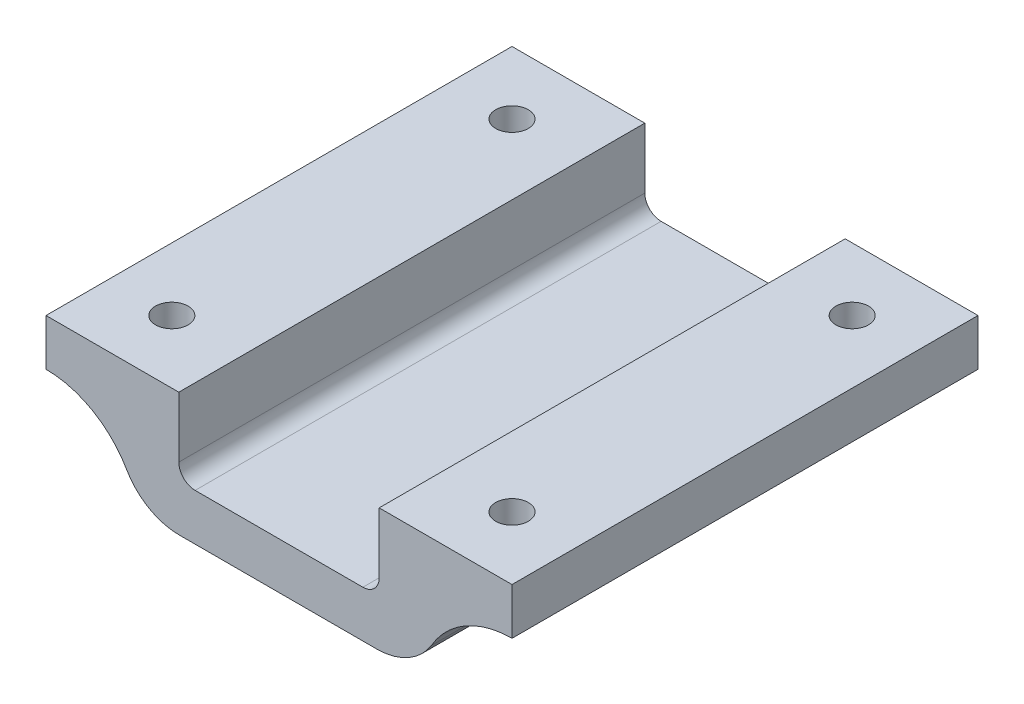
SolidWorks part; units mm, degrees
ref_plane "Front Plane" through (0, 0, 0) normal (0, 0, 1) x (1, 0, 0)
ref_plane "Top Plane" through (0, 0, 0) normal (0, 1, 0) x (1, 0, 0)
ref_plane "Right Plane" through (0, 0, 0) normal (1, 0, 0) x (0, 0, -1)
sketch "Sketch1" plane through (0, 0, 0) normal (0, 0, 1) x (1, 0, 0)
  line L0 (15, 13.2239) -> (35, 13.2239) construction
  line L1 (50, 10.2246) -> (50, 5.2246)
  line L2 (35.75, 10.2246) -> (50, 10.2246)
  line L3 (35.75, 3.7246) -> (35.75, 10.2246)
  line L4 (15, 22.2239) -> (15, 4.2239)
  line L5 (16, 3.2239) -> (34, 3.2239)
  line L6 (35, 4.2239) -> (35, 22.2239)
  line L7 (34, 23.2239) -> (16, 23.2239)
  line L8 (15, 22.2239) -> (15, 4.2239) construction
  line L9 (16, 3.2239) -> (34, 3.2239) construction
  line L10 (35, 4.2239) -> (35, 22.2239) construction
  line L11 (34, 23.2239) -> (16, 23.2239) construction
  line L12 (16, 1.9746) -> (34, 1.9746)
  line L13 (14.25, 10.2246) -> (14.25, 3.7246)
  line L14 (0, 10.2246) -> (14.25, 10.2246)
  line L15 (0, 5.2246) -> (0, 10.2246)
  line L16 (37.0096, 28.7233) -> (12.9904, 28.7233)
  line L17 (0, 21.2233) -> (0, 16.2233)
  line L18 (0, 16.2233) -> (14.25, 16.2233)
  line L19 (14.25, 16.2233) -> (14.25, 22.7233)
  line L20 (16, 24.4733) -> (34, 24.4733)
  line L21 (35.75, 22.7233) -> (35.75, 16.2233)
  line L22 (35.75, 16.2233) -> (50, 16.2233)
  line L23 (50, 16.2233) -> (50, 21.2233)
  line L24 (37.0096, 28.7233) -> (12.9904, 28.7233) construction
  line L25 (0, 21.2233) -> (0, 16.2233) construction
  line L26 (0, 16.2233) -> (14.25, 16.2233) construction
  line L27 (14.25, 16.2233) -> (14.25, 22.7233) construction
  line L28 (16, 24.4733) -> (34, 24.4733) construction
  line L29 (35.75, 22.7233) -> (35.75, 16.2233) construction
  line L30 (35.75, 16.2233) -> (50, 16.2233) construction
  line L31 (50, 16.2233) -> (50, 21.2233) construction
  line L33 (14.2894, -3.0254) -> (35.7106, -3.0254)
  arc A1 (41.3397, 0.2246) -> (50, 5.2246) centre (50, -4.7754) cw
  arc A2 (35.75, 3.7246) -> (34, 1.9746) centre (34, 3.7246) cw
  arc A3 (16, 1.9746) -> (14.25, 3.7246) centre (16, 3.7246) cw
  arc A4 (16, 23.2239) -> (15, 22.2239) centre (16, 22.2239) ccw
  arc A5 (15, 4.2239) -> (16, 3.2239) centre (16, 4.2239) ccw
  arc A6 (34, 3.2239) -> (35, 4.2239) centre (34, 4.2239) ccw
  arc A7 (35, 22.2239) -> (34, 23.2239) centre (34, 22.2239) ccw
  arc A8 (16, 23.2239) -> (15, 22.2239) centre (16, 22.2239) ccw construction
  arc A9 (15, 4.2239) -> (16, 3.2239) centre (16, 4.2239) ccw construction
  arc A10 (34, 3.2239) -> (35, 4.2239) centre (34, 4.2239) ccw construction
  arc A11 (35, 22.2239) -> (34, 23.2239) centre (34, 22.2239) ccw construction
  arc A12 (0, 5.2246) -> (8.6603, 0.2246) centre (0, -4.7754) cw
  arc A14 (12.9904, 28.7233) -> (8.6603, 26.2233) centre (12.9904, 23.7233) ccw
  arc A15 (0, 21.2233) -> (8.6603, 26.2233) centre (0, 31.2233) ccw
  arc A16 (16, 24.4733) -> (14.25, 22.7233) centre (16, 22.7233) ccw
  arc A17 (35.75, 22.7233) -> (34, 24.4733) centre (34, 22.7233) ccw
  arc A18 (41.3397, 26.2233) -> (50, 21.2233) centre (50, 31.2233) ccw
  arc A19 (41.3397, 26.2233) -> (37.0096, 28.7233) centre (37.0096, 23.7233) ccw
  arc A20 (12.9904, 28.7233) -> (8.6603, 26.2233) centre (12.9904, 23.7233) ccw construction
  arc A21 (0, 21.2233) -> (8.6603, 26.2233) centre (0, 31.2233) ccw construction
  arc A22 (16, 24.4733) -> (14.25, 22.7233) centre (16, 22.7233) ccw construction
  arc A23 (35.75, 22.7233) -> (34, 24.4733) centre (34, 22.7233) ccw construction
  arc A24 (41.3397, 26.2233) -> (50, 21.2233) centre (50, 31.2233) ccw construction
  arc A25 (41.3397, 26.2233) -> (37.0096, 28.7233) centre (37.0096, 23.7233) ccw construction
  arc A26 (8.6603, 0.2246) -> (14.2894, -3.0254) centre (14.2894, 3.4746) ccw
  arc A27 (35.7106, -3.0254) -> (41.3397, 0.2246) centre (35.4411, 3.9414) ccw
  point P52 (25, -3.0254)
  point P53 (25, 1.9746)
  dimension "D3" = 5
  dimension "D1" = 0
  dimension "D2" = 0
extrude "Boss-Extrude1" add sketch "Sketch1" against normal blind 50
sketch "Sketch2" plane through (0, -3.0254, 0) normal (0, -1, 0) x (1, 0, 0)
  circle A16 centre (6.75, -43.25) radius 1.75 construction
  circle A17 centre (43.25, -43.25) radius 1.75 construction
  circle A18 centre (6.75, -6.75) radius 1.75 construction
  circle A19 centre (43.25, -6.75) radius 1.75 construction
  circle A20 centre (6.75, -43.25) radius 1.75
  circle A21 centre (43.25, -43.25) radius 1.75
  circle A22 centre (6.75, -6.75) radius 1.75
  circle A23 centre (43.25, -6.75) radius 1.75
extrude "Cut-Extrude1" cut sketch "Sketch2" against normal through all
sketch "Sketch3" plane through (0, -3.0254, 0) normal (0, -1, 0) x (1, 0, 0)
  line L0 (25, 0) -> (25, -50) construction
  line L1 (9.75, -5.0179) -> (6.75, -3.2859)
  line L2 (6.75, -3.2859) -> (3.75, -5.0179)
  line L3 (3.75, -5.0179) -> (3.75, -8.4821)
  line L4 (3.75, -8.4821) -> (6.75, -10.2141)
  line L5 (6.75, -10.2141) -> (9.75, -8.4821)
  line L6 (9.75, -8.4821) -> (9.75, -5.0179)
  line L7 (6.7708, -39.786) -> (3.7605, -41.4999)
  line L8 (3.7605, -41.4999) -> (3.7396, -44.964)
  line L9 (3.7396, -44.964) -> (6.7292, -46.714)
  line L10 (6.7292, -46.714) -> (9.7395, -45.0001)
  line L11 (9.7395, -45.0001) -> (9.7604, -41.536)
  line L12 (9.7604, -41.536) -> (6.7708, -39.786)
  line L13 (14.2894, 0) -> (35.7106, 0) construction
  line L14 (35.7106, -50) -> (14.2894, -50) construction
  line L15 (25, -50) -> (0, -25) construction
  line L16 (0, -50) -> (0, 0) construction
  line L17 (0, -25) -> (50, -25) construction
  line L18 (50, -50) -> (50, 0) construction
  line L19 (40.2396, -41.536) -> (43.2292, -39.786)
  line L20 (40.2605, -45.0001) -> (40.2396, -41.536)
  line L21 (43.2708, -46.714) -> (40.2605, -45.0001)
  line L22 (46.2604, -44.964) -> (43.2708, -46.714)
  line L23 (46.2395, -41.4999) -> (46.2604, -44.964)
  line L24 (43.2292, -39.786) -> (46.2395, -41.4999)
  line L25 (40.25, -8.4821) -> (40.25, -5.0179)
  line L26 (43.25, -10.2141) -> (40.25, -8.4821)
  line L27 (46.25, -8.4821) -> (43.25, -10.2141)
  line L28 (46.25, -5.0179) -> (46.25, -8.4821)
  line L29 (43.25, -3.2859) -> (46.25, -5.0179)
  line L30 (40.25, -5.0179) -> (43.25, -3.2859)
  circle A0 centre (6.75, -6.75) radius 3 construction
  circle A1 centre (6.75, -43.25) radius 3 construction
  circle A2 centre (43.25, -43.25) radius 3 construction
  circle A3 centre (43.25, -6.75) radius 3 construction
  point P46 (5.2223, -26.6349)
  point P47 (6.75, -43.25)
  point P48 (6.75, -6.75)
  dimension "D1" = 6
extrude "Cut-Extrude2" cut sketch "Sketch3" against normal up to vertex (8.25 mm away) up to point (50, 5.2246, 0)
